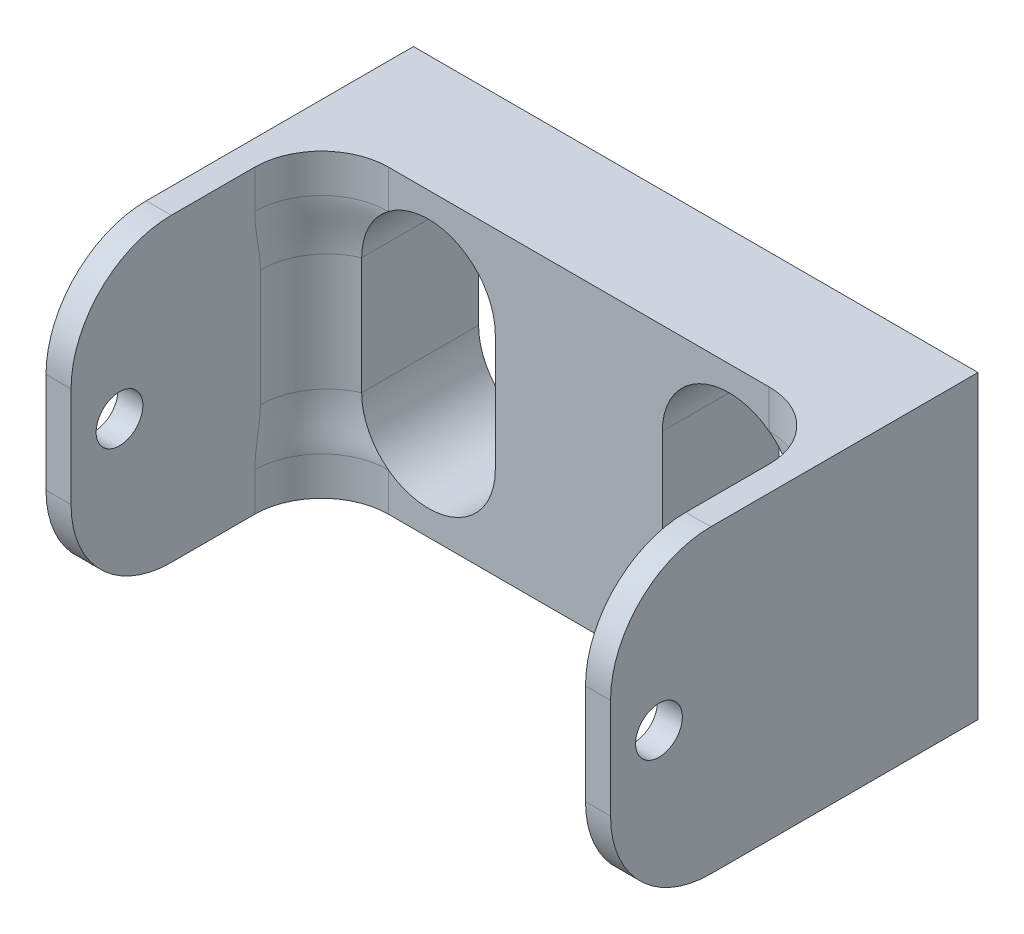
SolidWorks part; units mm, degrees
ref_plane "Front Plane" through (0, 0, 0) normal (0, 0, 1) x (1, 0, 0)
ref_plane "Top Plane" through (0, 0, 0) normal (0, 1, 0) x (1, 0, 0)
ref_plane "Right Plane" through (0, 0, 0) normal (1, 0, 0) x (0, 0, -1)
sketch "Sketch1" plane through (0, 0, 0) normal (0, 0, 1) x (1, 0, 0)
  line L0 (-9, 3.5) -> (-9, -3.5) construction
  line L1 (-16.9, -9) -> (16.9, -9)
  line L2 (-16.9, -9) -> (-16.9, 9)
  line L3 (-16.9, 9) -> (16.9, 9)
  line L4 (16.9, -9) -> (16.9, 9)
  line L5 (-16.9, -9) -> (16.9, 9) construction
  line L6 (-16.9, 9) -> (16.9, -9) construction
  line L7 (-5, 3.5) -> (-5, -3.5)
  line L8 (-13, 3.5) -> (-13, -3.5)
  line L9 (9, 3.5) -> (9, -3.5) construction
  line L10 (13, 3.5) -> (13, -3.5)
  line L11 (5, 3.5) -> (5, -3.5)
  arc A0 (-5, 3.5) -> (-13, 3.5) centre (-9, 3.5) ccw
  arc A1 (-13, -3.5) -> (-5, -3.5) centre (-9, -3.5) ccw
  arc A2 (13, 3.5) -> (5, 3.5) centre (9, 3.5) ccw
  arc A3 (5, -3.5) -> (13, -3.5) centre (9, -3.5) ccw
  point P0 (0, 0)
  point P8 (-9, 0)
  point P15 (9, 0)
  dimension "D1" = 33.8
  dimension "D2" = 18
  dimension "D3" = 8
  dimension "D4" = 7
  dimension "D5" = 8
  dimension "D6" = 7
  dimension "D7" = 10
  dimension "D8" = 5
extrude "Boss-Extrude1" add sketch "Sketch1" along normal blind 7
sketch "Sketch2" plane through (0, 0, 7) normal (0, 0, 1) x (1, 0, 0)
  line L0 (-16.9, -9) -> (16.9, -9) construction
  line L1 (-16.9, 9) -> (-15.4, 9)
  line L2 (-16.9, 9) -> (-16.9, -9)
  line L3 (-16.9, -9) -> (-15.4, -9)
  line L4 (-15.4, 9) -> (-15.4, -9)
  line L6 (16.9, 9) -> (15.4, 9)
  line L7 (16.9, 9) -> (16.9, -9)
  line L8 (16.9, -9) -> (15.4, -9)
  line L9 (15.4, 9) -> (15.4, -9)
  dimension "D1" = 1.5
  dimension "D2" = 1.5
extrude "Boss-Extrude2" add sketch "Sketch2" along normal blind 15
sketch "Sketch3" plane through (16.9, 0, 0) normal (1, 0, 0) x (0, 0, -1)
  line L0 (-22, -9) -> (-22, 9) construction
  circle A0 centre (-19.1, 0) radius 1.4
  point P2 (-22, 0)
  dimension "D1" = 2.8
  dimension "D2" = 2.9
extrude "Cut-Extrude1" cut sketch "Sketch3" against normal through all
fillet "Fillet1" radius 6 4 edges at (16.15, -9, 22) (-16.15, -9, 22) (-16.15, 9, 22) (16.15, 9, 22)
fillet "Fillet2" radius 4 2 edges at (15.4, 0, 7)
